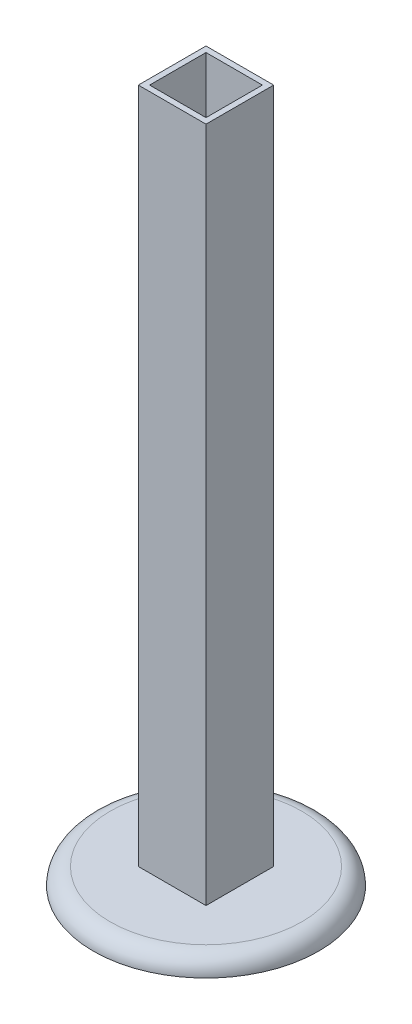
SolidWorks part; units mm, degrees
ref_plane "Front Plane" through (0, 0, 0) normal (0, 0, 1) x (1, 0, 0)
ref_plane "Top Plane" through (0, 0, 0) normal (0, 1, 0) x (1, 0, 0)
ref_plane "Right Plane" through (0, 0, 0) normal (1, 0, 0) x (0, 0, -1)
sketch "Sketch1" plane through (0, 0, 0) normal (0, 1, 0) x (1, 0, 0)
  circle A0 centre (0, 0) radius 200
  dimension "D1" = 400
extrude "Boss-Extrude1" add sketch "Sketch1" along normal blind 30
fillet "Fillet1" radius 30 1 edges at (0, 30, 200)
sketch "Sketch2" plane through (0, 30, 0) normal (0, 1, 0) x (1, 0, 0)
  line L1 (-60, -60) -> (60, -60)
  line L2 (-60, -60) -> (-60, 60)
  line L3 (-60, 60) -> (60, 60)
  line L4 (60, -60) -> (60, 60)
  line L5 (-60, -60) -> (60, 60) construction
  line L6 (-60, 60) -> (60, -60) construction
  point P0 (0, 0)
  dimension "D1" = 120
  dimension "D2" = 120
extrude "Boss-Extrude2" add sketch "Sketch2" along normal blind 1200
shell "Shell1" thickness 10 removed face at (0, 1230, 0)
sketch "Sketch3" plane through (0, 1230, 0) normal (0, 1, 0) x (1, 0, 0)
  line L1 (-60, -60) -> (60, -60)
  line L2 (-60, -60) -> (-60, 60)
  line L3 (-60, 60) -> (60, 60)
  line L4 (60, -60) -> (60, 60)
  line L5 (-60, -60) -> (60, 60) construction
  line L6 (-60, 60) -> (60, -60) construction
  point P0 (0, 0)
  point P8 (0, 0)
